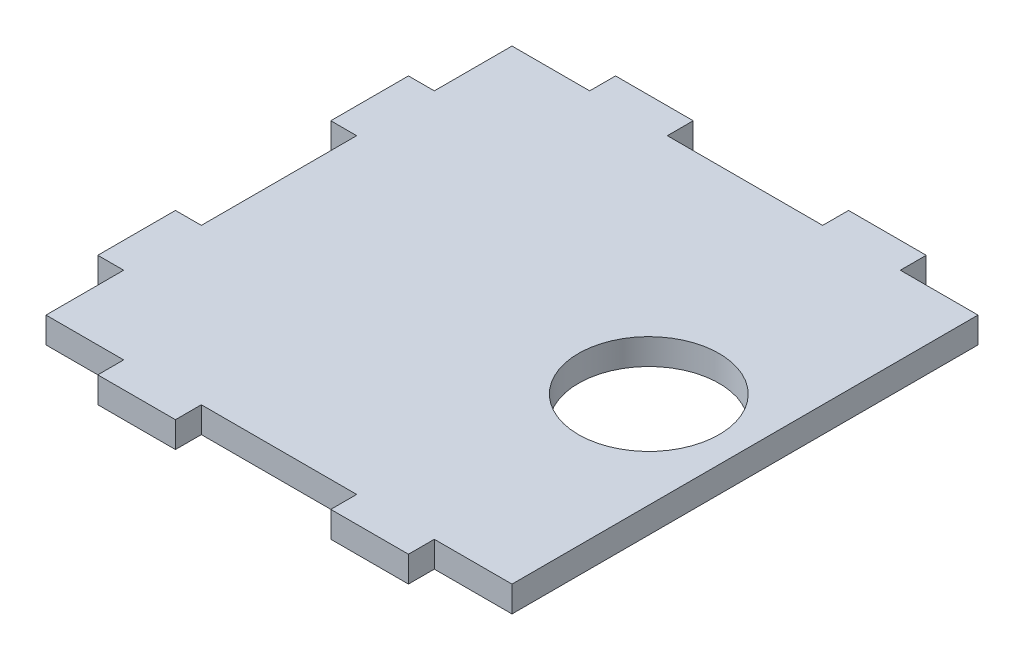
SolidWorks part; units mm, degrees
ref_plane "Front Plane" through (0, 0, 0) normal (0, 0, 1) x (1, 0, 0)
ref_plane "Top Plane" through (0, 0, 0) normal (0, 1, 0) x (1, 0, 0)
ref_plane "Right Plane" through (0, 0, 0) normal (1, 0, 0) x (0, 0, -1)
sketch "Sketch1" plane through (0, 0, 0) normal (0, 1, 0) x (1, 0, 0)
  line L0 (0, 57.15) -> (184.6638, 57.15) construction
  line L1 (0, 0) -> (19.05, 0)
  line L2 (0, 0) -> (0, 19.05)
  line L3 (0, 114.3) -> (19.05, 114.3)
  line L4 (114.3, 0) -> (114.3, 114.3)
  line L5 (38.1, 0) -> (76.2, 0)
  line L7 (95.25, 0) -> (95.25, -6.35)
  line L8 (95.25, -6.35) -> (76.2, -6.35)
  line L9 (76.2, 0) -> (76.2, -6.35)
  line L11 (19.05, 0) -> (19.05, -6.35)
  line L12 (19.05, -6.35) -> (38.1, -6.35)
  line L13 (38.1, 0) -> (38.1, -6.35)
  line L14 (95.25, 0) -> (114.3, 0)
  line L15 (38.1, 114.3) -> (38.1, 120.65)
  line L16 (19.05, 120.65) -> (38.1, 120.65)
  line L17 (19.05, 114.3) -> (19.05, 120.65)
  line L18 (76.2, 114.3) -> (76.2, 120.65)
  line L19 (95.25, 120.65) -> (76.2, 120.65)
  line L20 (95.25, 114.3) -> (95.25, 120.65)
  line L21 (38.1, 114.3) -> (76.2, 114.3)
  line L23 (95.25, 114.3) -> (114.3, 114.3)
  line L24 (-6.35, 19.05) -> (-6.35, 38.1)
  line L25 (0, 95.25) -> (-6.35, 95.25)
  line L27 (0, 76.2) -> (-6.35, 76.2)
  line L28 (-6.35, 95.25) -> (-6.35, 76.2)
  line L29 (0, 38.1) -> (-6.35, 38.1)
  line L31 (0, 19.05) -> (-6.35, 19.05)
  line L32 (0, 95.25) -> (0, 114.3)
  line L33 (0, 38.1) -> (0, 76.2)
  dimension "D1" = 114.3
  dimension "D2" = 114.3
  dimension "D3" = 19.05
  dimension "D4" = 19.05
  dimension "D5" = 19.05
  dimension "D6" = 19.05
  dimension "D7" = 6.35
  dimension "D8" = 6.35
  dimension "D9" = 19.05
  dimension "D10" = 19.05
extrude "Boss-Extrude1" add sketch "Sketch1" against normal blind 6.35
sketch "Sketch2" plane through (0, 0, 0) normal (0, 1, 0) x (1, 0, 0)
  line L0 (114.3, 57.15) -> (55.59, 57.15) construction
  line L1 (114.3, 0) -> (114.3, 114.3) construction
  line L2 (107.95, 57.15) -> (107.95, 78.6846) construction
  circle A0 centre (90.7, 57.15) radius 17.25
  point P8 (0, 0)
  dimension "D1" = 34.5001
  dimension "D2" = 6.35
extrude "Cut-Extrude1" cut sketch "Sketch2" against normal through all
